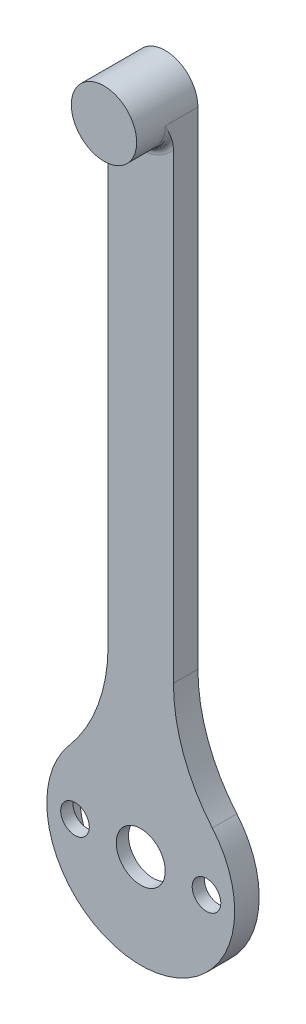
SolidWorks part; units mm, degrees
ref_plane "Plan de face" through (0, 0, 0) normal (0, 0, 1) x (1, 0, 0)
ref_plane "Plan de dessus" through (0, 0, 0) normal (0, 1, 0) x (1, 0, 0)
ref_plane "Plan de droite" through (0, 0, 0) normal (1, 0, 0) x (0, 0, -1)
sketch "Esquisse1" plane through (0, 0, 0) normal (0, 0, 1) x (1, 0, 0)
  line L0 (-4, 0) -> (-4, -69.2181)
  line L1 (4, 0) -> (4, -69.2181)
  arc A0 (4, 0) -> (-4, 0) centre (0, 0) ccw
  arc A1 (-4, -69.2181) -> (4, -69.2181) centre (0, -80) ccw
  dimension "D1" = 8
  dimension "D2" = 80
  dimension "D3" = 23
extrude "Boss.-Extru.1" add sketch "Esquisse1" along normal blind 3
sketch "Esquisse2" plane through (0, 0, 0) normal (0, 0, 1) x (1, 0, 0)
  line L0 (0, -55) -> (0, 55) construction
  circle A0 centre (0, -80) radius 10.5
  arc A1 (-4, -69.2181) -> (4, -69.2181) centre (0, -80) ccw construction
  point P4 (0, 0)
  dimension "D1" = 21
extrude "Enlèv. mat.-Extru.3" cut sketch "Esquisse2" along normal blind 1.5
sketch "Esquisse3" plane through (0, 0, 0) normal (0, 0, 1) x (1, 0, 0)
  line L0 (0, -55) -> (0, 55) construction
  circle A0 centre (0, -80) radius 3
  arc A1 (-4, -69.2181) -> (4, -69.2181) centre (0, -80) ccw construction
  dimension "D1" = 6
extrude "Enlèv. mat.-Extru.5" cut sketch "Esquisse3" along normal through all
sketch "Esquisse4" plane through (0, 0, 3) normal (0, 0, 1) x (1, 0, 0)
  circle A0 centre (0, 0) radius 4
extrude "Boss.-Extru.2" add sketch "Esquisse4" along normal blind 4.5
fillet "Congé1" radius 20 2 edges at (4, -69.2181, 1.5) (-4, -69.2181, 1.5)
fillet "Congé2" radius 1 1 edges at (0, -4, 3)
sketch "Esquisse5" plane through (0, 0, 3) normal (0, 0, 1) x (1, 0, 0)
  circle A0 centre (-8.05, -80) radius 1.75
  circle A1 centre (8.05, -80) radius 1.75
  circle A2 centre (0, -80) radius 6.3 construction
  arc A3 (-8.7619, -72.5516) -> (8.7619, -72.5516) centre (0, -80) ccw construction
  point P6 (7.2993, -62.2651)
  dimension "D1" = 3.5
  dimension "D2" = 3.5
  dimension "D3" = 12.6
extrude "Enlèv. mat.-Extru.6" cut sketch "Esquisse5" against normal through all
